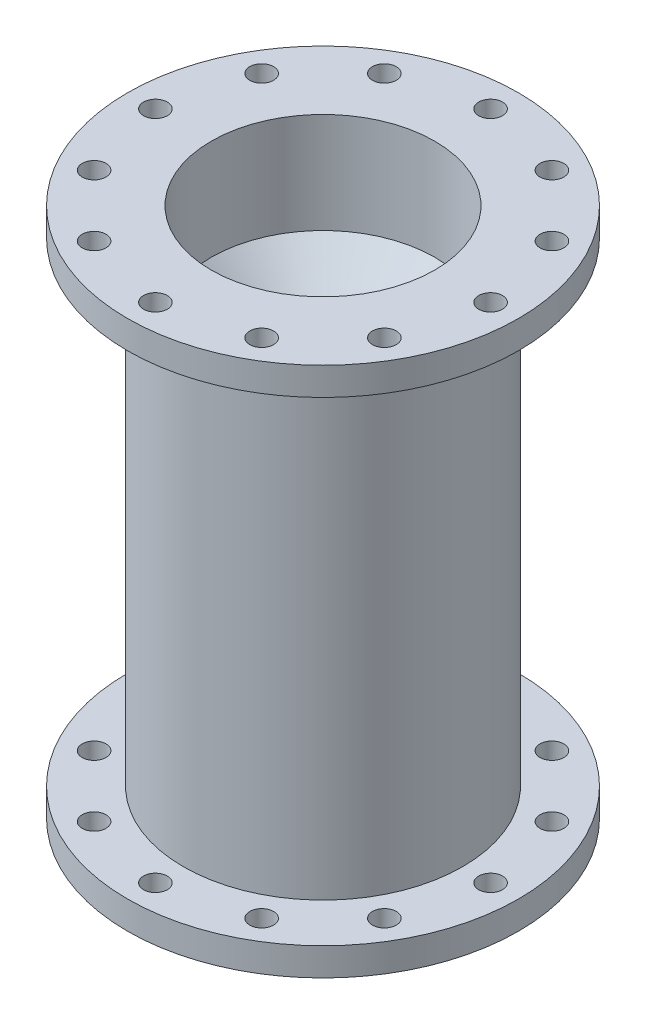
SolidWorks part; units mm, degrees
ref_plane "Front Plane" through (0, 0, 0) normal (0, 0, 1) x (1, 0, 0)
ref_plane "Top Plane" through (0, 0, 0) normal (0, 1, 0) x (1, 0, 0)
ref_plane "Right Plane" through (0, 0, 0) normal (1, 0, 0) x (0, 0, -1)
sketch "Sketch1" plane through (0, 0, 0) normal (1, 0, 0) x (0, 0, -1)
  line L1 (31.75, 6.35) -> (31.75, 114.3)
  line L8 (31.75, 120.65) -> (44.45, 120.65)
  line L9 (44.45, 120.65) -> (44.45, 114.3)
  line L10 (44.45, 114.3) -> (31.75, 114.3)
  line L11 (31.75, 0) -> (44.45, 0)
  line L12 (44.45, 0) -> (44.45, 6.35)
  line L13 (44.45, 6.35) -> (31.75, 6.35)
  line L27 (25.4, 114.3) -> (25.4, 120.65)
  line L28 (25.4, 120.65) -> (31.75, 120.65)
  line L29 (25.4, 6.35) -> (25.4, 0)
  line L30 (25.4, 0) -> (31.75, 0)
  line L31 (25.4, 114.3) -> (25.4, 6.35)
  line L32 (25.4, 0) -> (0, 0) construction
  line L33 (0, 0) -> (0, 6.35) construction
  dimension "D1" = 6.35
  dimension "D2" = 6.35
  dimension "D3" = 12.7
  dimension "D4" = 12.7
  dimension "D5" = 12.7
  dimension "D6" = 12.7
  dimension "D7" = 107.95
  dimension "D8" = 25.4
  dimension "D9" = 6.35
revolve "Chamber" add sketch "Sketch1" angle 360 about L33
sketch "Sketch4" plane through (0, 0, 0) normal (1, 0, 0) x (0, 0, -1)
  line L0 (0, 0) -> (0, 120.65) construction
  line L1 (25.4, 120.65) -> (-25.4, 120.65) construction
  line L8 (0, 60.325) -> (57.15, 60.325) construction
  line L15 (0, 0) -> (25.4, 0) construction
  line L16 (25.4, 0) -> (25.4, 95.25) construction
  line L17 (25.4, 97.79) -> (7.62, 97.79) construction
  line L18 (7.62, 97.79) -> (7.62, 80.01) construction
  line L22 (25.4, 95.25) -> (25.4, 97.79)
  line L23 (25.4, 97.79) -> (7.62, 80.01)
  line L24 (7.62, 80.01) -> (7.62, 77.47)
  line L25 (7.62, 77.47) -> (25.4, 95.25)
  dimension "D2" = 25.4
  dimension "D3" = 95.25
  dimension "D1" = 7.62
  dimension "D4" = 2.54
revolve "Turbulence Rings" add sketch "Sketch4" angle 360 about L0
sketch "Sketch5" plane through (0, 120.65, 0) normal (0, 1, 0) x (1, 0, 0)
  line L0 (0, 0) -> (-38.1, 0) construction
  line L1 (0, 0) -> (-32.9956, 19.05) construction
  circle A0 centre (0, 0) radius 38.1 construction
  point P0 (0, 0)
  point P5 (-38.1, 0)
  point P9 (-32.9956, 19.05)
  point P10 (-19.05, 32.9956)
  point P11 (0, 38.1)
  point P12 (19.05, 32.9956)
  point P13 (32.9956, 19.05)
  point P14 (38.1, 0)
  point P15 (32.9956, -19.05)
  point P16 (19.05, -32.9956)
  point P17 (0, -38.1)
  point P18 (-19.05, -32.9956)
  point P19 (-32.9956, -19.05)
  point P20 (0, 0)
  point P21 (0, 0)
  point P24 (0, 0)
  point P26 (0, 0)
  dimension "D3" = 38.1
  dimension "D1" = 30
  dimension "D2" = 12
hole_wizard "#3 (0.213) Diameter Hole3" positions "Sketch5" profile "Sketch9" hole size "#3" standard "ANSI Inch" end condition through all
sketch "Sketch9" plane through (0, 120.65, 0) normal (1, 0, 0) x (0, 0, 1)
  line L0 (0, 0) -> (0, 120.65)
  line L1 (0, 120.65) -> (2.7051, 120.65)
  line L2 (2.7051, 120.65) -> (2.7051, 0)
  line L5 (2.7051, 0) -> (0, 0)
  line L11 (0, -6.35) -> (0, 107.95) construction
  dimension "Thru Hole Dia." = 5.4102
  dimension "Thru Hole Depth" = 120.65
equation "\"Thickness of Material\"= 0.3in"
equation "\"Chamber Length\"= 4.25in"
equation "\"Flange Length\"= 0.5in"
equation "\"Chamber Wall Thickness\"= 0.25in"
equation "\"Ring Length\"= 1.2in"
equation "\"Ring Thickness\"= 0.1in"
equation "\"Number of Rings\"= 2"
equation "\"Chamber Radius\"= 1in"
equation "\"D7@Sketch1\"= \"Chamber Length\""
equation "\"D9@Sketch1\"= \"Chamber Wall Thickness\""
equation "\"D8@Sketch1\"= \"Chamber Radius\""
equation "\"Flange Thickness\"= 0.25in"
equation "\"D1@Sketch1\"= \"Flange Thickness\""
equation "\"D3@Sketch5\"= \"Chamber Radius\" + \"Chamber Wall Thickness\" + ( \"Flange to Inner Wall Length\" / 2 )"
equation "\"Flange to Inner Wall Length\"= ( \"Chamber Radius\" + \"Chamber Wall Thickness\" + \"Flange Length\" ) - ( \"Chamber Radius\" + \"Chamber Wall Thickness\" )"
equation "\"D2@Sketch4\"= \"Chamber Radius\""
equation "\"Turbulence Ring Distance from Face\"= 3.75in"
equation "\"D3@Sketch4\"= \"Turbulence Ring Distance from Face\""
equation "\"D4@Sketch1\"= \"Flange Length\""
equation "\"D3@Sketch1\"= \"Flange Length\""
equation "\"D5@Sketch1\"= \"Flange Length\""
equation "\"D6@Sketch1\"= \"Flange Length\""
equation "\"Center to Ring Edge Distance\"= 0.3 * ( \"Chamber Radius\" )"
equation "\"D1@Sketch4\"= \"Center to Ring Edge Distance\""
equation "\"D4@Sketch4\"= \"Ring Thickness\""
